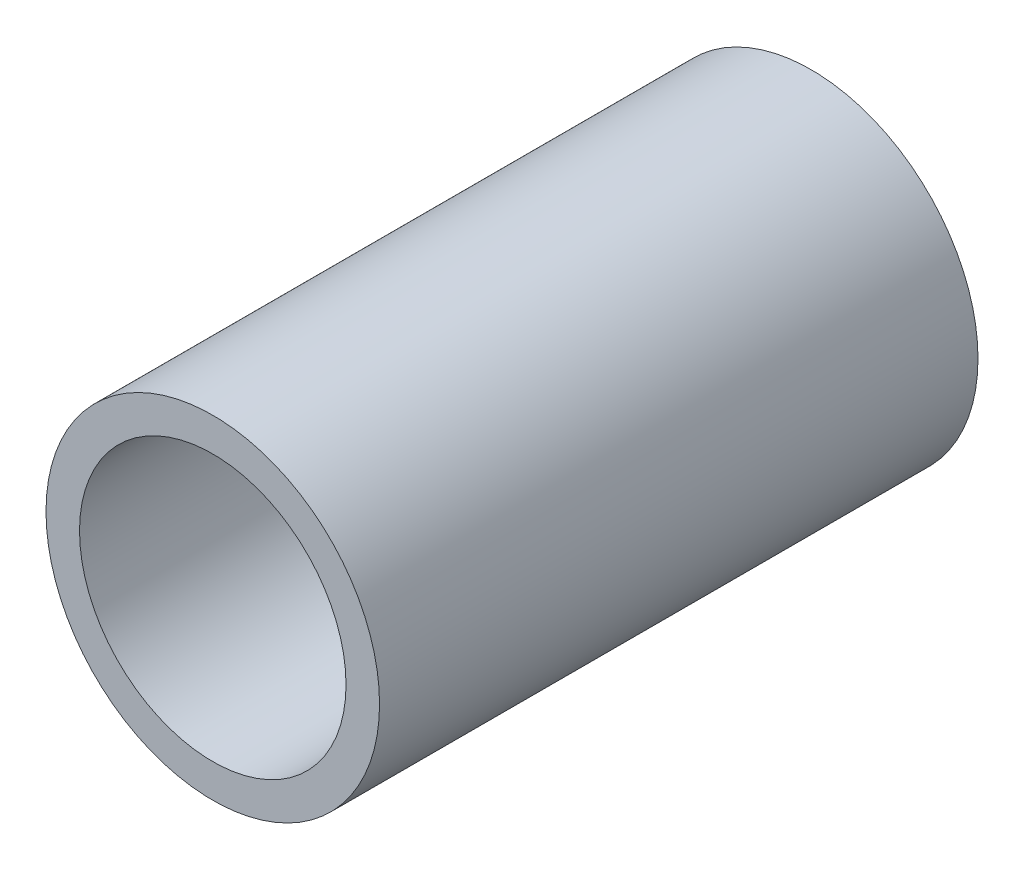
SolidWorks part; units mm, degrees
material "Leaded Commercial Bronze"
ref_plane "Front Plane" through (0, 0, 0) normal (0, 0, 1) x (1, 0, 0)
ref_plane "Top Plane" through (0, 0, 0) normal (0, 1, 0) x (1, 0, 0)
ref_plane "Right Plane" through (0, 0, 0) normal (1, 0, 0) x (0, 0, -1)
sketch "Sketch1" plane through (0, 0, 0) normal (0, 0, 1) x (1, 0, 0)
  circle A0 centre (0, 0) radius 7.9629
  circle A1 centre (0, 0) radius 6.3627
  dimension "OD" = 15.9258
  dimension "ID" = 12.7254
sketch "Sketch2" plane through (0, 0, 0) normal (1, 0, 0) x (0, 0, -1)
  line L2 (14.2875, 0) -> (-14.2875, 0) construction
  line L4 (-14.2875, -7.9629) -> (-14.2875, 7.9629) construction
  line L5 (-14.2875, -6.3627) -> (14.2875, -6.3627)
  line L6 (14.2875, 6.3627) -> (-14.2875, 6.3627)
  line L7 (14.2875, -7.9629) -> (14.2875, 7.9629) construction
  line L8 (-14.2875, 7.9629) -> (14.2875, 7.9629) construction
  line L9 (-14.2875, -7.9629) -> (14.2875, -7.9629) construction
  line L10 (0, 7.9629) -> (0, -7.9629) construction
  line L11 (0, 6.3627) -> (0, -6.3627) construction
  point P4 (0, -6.3627)
  point P7 (0, 6.3627)
  point P8 (0, 0)
  point P12 (-14.2875, 0)
  point P15 (14.2875, 0)
  point P16 (0, -7.9629)
  point P17 (0, 7.9629)
  dimension "Length" = 28.575
sketch "Sketch5" plane through (0, 0, 0) normal (0, 0, 1) x (1, 0, 0)
  circle A1 centre (0, 0) radius 6.3627
  circle A2 centre (0, 0) radius 6.3627
  circle A3 centre (0, 0) radius 7.9629
  circle A4 centre (0, 0) radius 7.9629
  dimension "D1" = 0
  dimension "D2" = 0
extrude "Boss-Extrude1" add sketch "Sketch5" along normal up to vertex and the other way up to vertex up to point (0, 0, 14.2875) other way up to point (0, 0, -14.2875)
sketch "Sketch4" plane through (0, 0, 14.2875) normal (0, 0, 1) x (1, 0, 0)
  line L0 (0, 0) -> (-4.4991, 4.4991)
  line L2 (0, -7.9629) -> (0, 7.9629) construction
  circle A1 centre (0, 0) radius 6.3627 construction
  dimension "D1" = 45
equation "\"D1\"= \"Length@Sketch2\""
